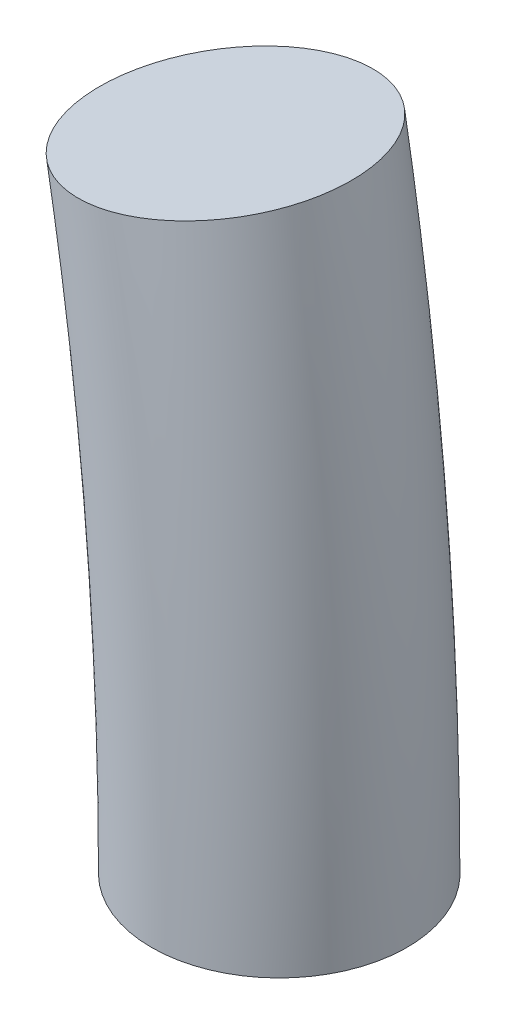
SolidWorks part; units mm, degrees
ref_plane "Front Plane" through (0, 0, 0) normal (0, 0, 1) x (1, 0, 0)
ref_plane "Top Plane" through (0, 0, 0) normal (0, 1, 0) x (1, 0, 0)
ref_plane "Right Plane" through (0, 0, 0) normal (1, 0, 0) x (0, 0, -1)
sketch "Sketch1" plane through (0, 0, 0) normal (0, 1, 0) x (1, 0, 0)
  line L0 (0, 33.9382) -> (0, -33.9382) construction
  point P4 (0, 0)
sketch "Sketch4" [suppressed] plane through (0, 0, 0) normal (0, 1, 0) x (0, 0, -1)
  line L0 (0, -34) -> (6.035, -34)
  line L4 (-6.035, -34) -> (0, -34)
  line L8 (6.035, -34) -> (9.4991, -40)
  line L9 (9.4991, -40) -> (-9.4991, -40)
  line L10 (-9.4991, -40) -> (-6.035, -34)
  dimension "D3" = 12.07
  dimension "D5" = 60
  dimension "D6" = 60
  dimension "D7" = 6
sketch "Sketch2" plane through (0, 0, 0) normal (0, 0, 1) x (1, 0, 0)
  line L2 (6.8966, -39.401) -> (-105.6552, -59.1015) construction
  line L3 (-105.6552, 59.1015) -> (6.8966, 39.401) construction
  line L4 (0, 0) -> (39.3923, 6.9459) construction
  line L5 (0, 0) -> (40, 0) construction
  arc A0 (6.8966, 39.401) -> (6.8966, -39.401) centre (0, 0) cw construction
  arc A1 (-105.6552, -59.1015) -> (-105.6552, 59.1015) centre (-116, 0) cw construction
  arc A2 (40, 0) -> (39.3923, 6.9459) centre (0, 0) ccw
  dimension "D1" = 40
  dimension "D2" = 60
  dimension "D3" = 116
  dimension "D4" = 10
sweep "VBeltSweep" [suppressed] add profiles "Sketch4" path "Sketch2"
sketch "Sketch12" plane through (0, 0, 0) normal (0, 1, 0) x (0, 0, -1)
  circle A0 centre (0, -41.5) radius 1.5
  dimension "D1" = 3
  dimension "D2" = 40
sweep "RoundBeltSweep" add profiles "Sketch12" path "Sketch2<2>"
sketch "Sketch2<2>" plane through (0, 0, 0) normal (0, 0, 1) x (1, 0, 0) same geometry as "Sketch2"
